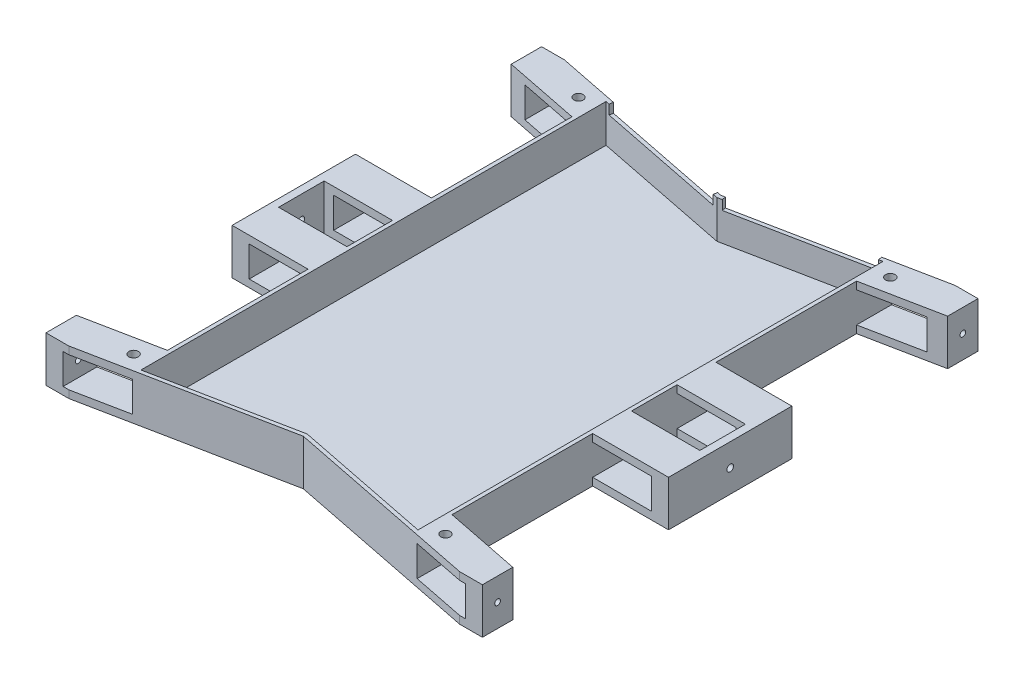
SolidWorks part; units mm, degrees
material "ABS"
ref_plane "Front Plane" through (0, 0, 0) normal (0, 0, 1) x (1, 0, 0)
ref_plane "Top Plane" through (0, 0, 0) normal (0, 1, 0) x (1, 0, 0)
ref_plane "Right Plane" through (0, 0, 0) normal (1, 0, 0) x (0, 0, -1)
sketch "Sketch1" plane through (0, 0, 0) normal (0, 1, 0) x (1, 0, 0)
  line L1 (-55, 0) -> (55, 0) construction
  line L2 (115, 32.5) -> (115, -32.5)
  line L3 (115, -32.5) -> (75, -32.5)
  line L4 (75, -32.5) -> (75, -106.6)
  line L5 (75, -106.6) -> (115, -114.6)
  line L6 (115, -114.6) -> (115, -130.6)
  line L7 (115, -130.6) -> (103, -130.6)
  line L8 (103, -130.6) -> (0, -110)
  line L9 (0, -55) -> (0, 55) construction
  line L11 (-115, 32.5) -> (-115, -32.5)
  line L12 (-115, -32.5) -> (-75, -32.5)
  line L13 (-75, -32.5) -> (-75, -106.6)
  line L14 (-75, -106.6) -> (-115, -114.6)
  line L15 (-115, -114.6) -> (-115, -130.6)
  line L16 (-115, -130.6) -> (-103, -130.6)
  line L17 (-103, -130.6) -> (0, -110)
  line L18 (115, 32.5) -> (75, 32.5)
  line L19 (75, 32.5) -> (75, 106.6)
  line L20 (115, 130.6) -> (103, 130.6)
  line L21 (115, 114.6) -> (115, 130.6)
  line L22 (75, 106.6) -> (115, 114.6)
  line L23 (103, 130.6) -> (0, 110)
  line L24 (-115, 114.6) -> (-115, 130.6)
  line L25 (-115, 130.6) -> (-103, 130.6)
  line L26 (-103, 130.6) -> (0, 110)
  line L27 (-75, 106.6) -> (-115, 114.6)
  line L28 (-115, 32.5) -> (-75, 32.5)
  line L29 (-75, 32.5) -> (-75, 106.6)
  line L30 (75, -106.6) -> (75, -125) construction
  line L32 (-75, -106.6) -> (-75, -125) construction
  line L34 (-75, 106.6) -> (-75, 125) construction
  line L36 (75, 106.6) -> (75, 125) construction
  point P21 (115, 0)
  point P33 (-115, 0)
  dimension "D1" = 250
  dimension "D2" = 220
  dimension "D3" = 150
  dimension "D4" = 16
  dimension "D5" = 12
  dimension "D6" = 65
  dimension "D7" = 40
extrude "Boss-Extrude1" add sketch "Sketch1" along normal blind 12 and the other way blind 12
sketch "Sketch2" plane through (0, 0, 130.6) normal (0, 0, 1) x (1, 0, 0)
  line L0 (-115, -12) -> (-115, 12) construction
  line L1 (-106, -8) -> (106, -8)
  line L2 (-106, -8) -> (-106, 8)
  line L3 (-106, 8) -> (106, 8)
  line L4 (106, -8) -> (106, 8)
  line L5 (115, -12) -> (115, 12) construction
  line L7 (55, 0) -> (-55, 0) construction
  dimension "D1" = 8
  dimension "D2" = 8
  dimension "D3" = 9
  dimension "D4" = 9
extrude "Cut-Extrude1" cut sketch "Sketch2" against normal blind 320
sketch "Sketch4" plane through (0, 12, 0) normal (0, 1, 0) x (1, 0, 0)
  line L0 (-55, 0) -> (55, 0) construction
  line L1 (-111, 12) -> (-75, 12)
  line L2 (-111, 12) -> (-111, -12)
  line L3 (-111, -12) -> (-75, -12)
  line L4 (-75, 12) -> (-75, -12)
  line L5 (-115, 32.5) -> (-115, -32.5) construction
  line L6 (-75, -32.5) -> (-75, -106.6) construction
  line L7 (0, -55) -> (0, 55) construction
  line L8 (111, -12) -> (75, -12)
  line L9 (75, 12) -> (75, -12)
  line L10 (111, 12) -> (75, 12)
  line L11 (111, 12) -> (111, -12)
  dimension "D1" = 12
  dimension "D2" = 12
  dimension "D3" = 4
extrude "Cut-Extrude2" cut sketch "Sketch4" against normal blind 24
sketch "Sketch6" plane through (0, 0, 0) normal (1, 0, 0) x (0, 0, -1)
  line L0 (-114.6, 0) -> (-130.6, 0) construction
  line L1 (114.6, 0) -> (130.6, 0) construction
  circle A0 centre (-122.6, 0) radius 1.5
  circle A1 centre (122.6, 0) radius 1.5
  point P6 (-122.6, 0)
  point P10 (122.6, 0)
  dimension "D1" = 3
extrude "Cut-Extrude3" cut sketch "Sketch6" against normal through all both and the other way through all
sketch "Sketch7" plane through (115, 0, 0) normal (1, 0, 0) x (0, 0, -1)
  circle A0 centre (0, 0) radius 1.75
  dimension "D1" = 3.5
extrude "Cut-Extrude4" cut sketch "Sketch7" against normal up to surface (230 mm away) up to face at (-115, 0, 0)
sketch "Sketch8" plane through (0, 12, 0) normal (0, 1, 0) x (1, 0, 0)
  line L0 (0, 110) -> (0, -110) construction
  line L1 (106, -12) -> (106, 12) construction
  line L2 (106, 8) -> (94, 8)
  line L3 (106, 8) -> (106, -8)
  line L4 (106, -8) -> (94, -8)
  line L5 (94, 8) -> (94, -8)
  line L6 (-106, 0) -> (115, 0) construction
  line L7 (-106, 12) -> (-106, -12) construction
  line L8 (115, -32.5) -> (115, 32.5) construction
  line L9 (-106, -8) -> (-94, -8)
  line L10 (-94, 8) -> (-94, -8)
  line L11 (-106, 8) -> (-94, 8)
  line L12 (-106, 8) -> (-106, -8)
  point P16 (94, 0)
  dimension "D1" = 16
  dimension "D2" = 12
extrude "Cut-Extrude5" [suppressed] cut sketch "Sketch8" against normal up to surface (5 mm away) up to face at (0, 8, 0)
sketch "Sketch11" plane through (0, 12, 0) normal (0, 1, 0) x (1, 0, 0)
  line L0 (-75, -125) -> (-75, 125)
  line L1 (-103, -130.6) -> (0, -110) construction
  line L2 (0, 110) -> (-103, 130.6) construction
  line L3 (75, 125) -> (75, -125)
  line L4 (103, 130.6) -> (0, 110) construction
  line L5 (0, -110) -> (103, -130.6) construction
  line L6 (75, 32.5) -> (75, 106.6) construction
  line L7 (-75, 106.6) -> (-75, 32.5) construction
  line L8 (0, -110) -> (75, -125)
  line L9 (-75, -125) -> (0, -110)
  line L10 (0, 110) -> (-75, 125)
  line L11 (75, 125) -> (0, 110)
extrude "Cut-Extrude7" cut sketch "Sketch11" against normal up to surface (4 mm away) up to face at (0, 8, 0)
sketch "Sketch12" plane through (0, -8, 0) normal (0, 1, 0) x (1, 0, 0)
  line L0 (-75, 125) -> (-75, -125)
  line L1 (-103, -130.6) -> (0, -110) construction
  line L2 (75, 125) -> (75, -125)
  line L3 (-75, -125) -> (0, -110)
  line L4 (0, -110) -> (75, -125)
  line L5 (-75, 125) -> (0, 110)
  line L6 (0, 110) -> (75, 125)
  line L7 (0, 107.9604) -> (73, 122.5604)
  line L8 (73, 122.5604) -> (73, -122.5604)
  line L9 (0, -107.9604) -> (73, -122.5604)
  line L10 (-73, -122.5604) -> (0, -107.9604)
  line L11 (-73, 122.5604) -> (-73, -122.5604)
  line L12 (-73, 122.5604) -> (0, 107.9604)
  dimension "D1" = 2
extrude "Boss-Extrude2" add sketch "Sketch12" along normal blind 20
sketch "Sketch14" plane through (0, 12, 0) normal (0, 1, 0) x (1, 0, 0)
  line L0 (0, 110) -> (0, -110) construction
  line L1 (75, 0) -> (-75, 0) construction
  line L2 (75, -12) -> (75, 12) construction
  line L3 (-75, 12) -> (-75, -12) construction
  line L4 (-83.9461, 108.3892) -> (-80.4076, 126.0815) construction
  line L5 (-115, 114.6) -> (-75, 106.6) construction
  line L6 (0, 110) -> (-103, 130.6) construction
  circle A0 centre (-82.1768, 117.2354) radius 2.5
  circle A1 centre (82.1768, 117.2354) radius 2.5
  circle A2 centre (82.1768, -117.2354) radius 2.5
  circle A3 centre (-82.1768, -117.2354) radius 2.5
  dimension "D2" = 5
  dimension "D1" = 82
extrude "Cut-Extrude8" cut sketch "Sketch14" against normal up to next
sketch "Sketch15" plane through (0, 12, 0) normal (0, 1, 0) x (1, 0, 0)
  line L0 (-71.0388, 122.1682) -> (-70.6466, 124.1293)
  line L1 (0, 110) -> (-103, 130.6) construction
  line L2 (0, 107.9604) -> (-73, 122.5604) construction
  line L3 (-2.3982, 108.44) -> (-71.0388, 122.1682)
  line L4 (-2.006, 110.4012) -> (-70.6466, 124.1293)
  line L5 (73, 122.5604) -> (0, 107.9604) construction
  line L6 (103, 130.6) -> (0, 110) construction
  line L7 (71.0388, 122.1682) -> (2.3982, 108.44)
  line L8 (70.6466, 124.1293) -> (2.006, 110.4012)
  line L10 (-2.3982, 108.44) -> (-2.006, 110.4012)
  line L11 (2.3982, 108.44) -> (2.006, 110.4012)
  line L12 (70.6466, 124.1293) -> (71.0388, 122.1682)
  dimension "D1" = 70
  dimension "D2" = 70
  dimension "D3" = 2
  dimension "D4" = 2
extrude "Cut-Extrude9" cut sketch "Sketch15" against normal blind 5
equation "\"A\"= 4"
equation "\"D1@Boss-Extrude1\"=3*\"A\""
equation "\"D2@Boss-Extrude1\"=3*\"A\""
equation "\"D1@Sketch2\"=2*\"A\""
equation "\"D2@Sketch2\"=2*\"A\""
equation "\"D1@Sketch4\"=3*\"A\""
equation "\"D2@Sketch4\"=3*\"A\""
equation "\"D3@Sketch4\"=\"A\""
equation "\"D1@Cut-Extrude2\"=6*\"A\""
equation "\"D1@Cut-Extrude1\"=80*\"A\""
